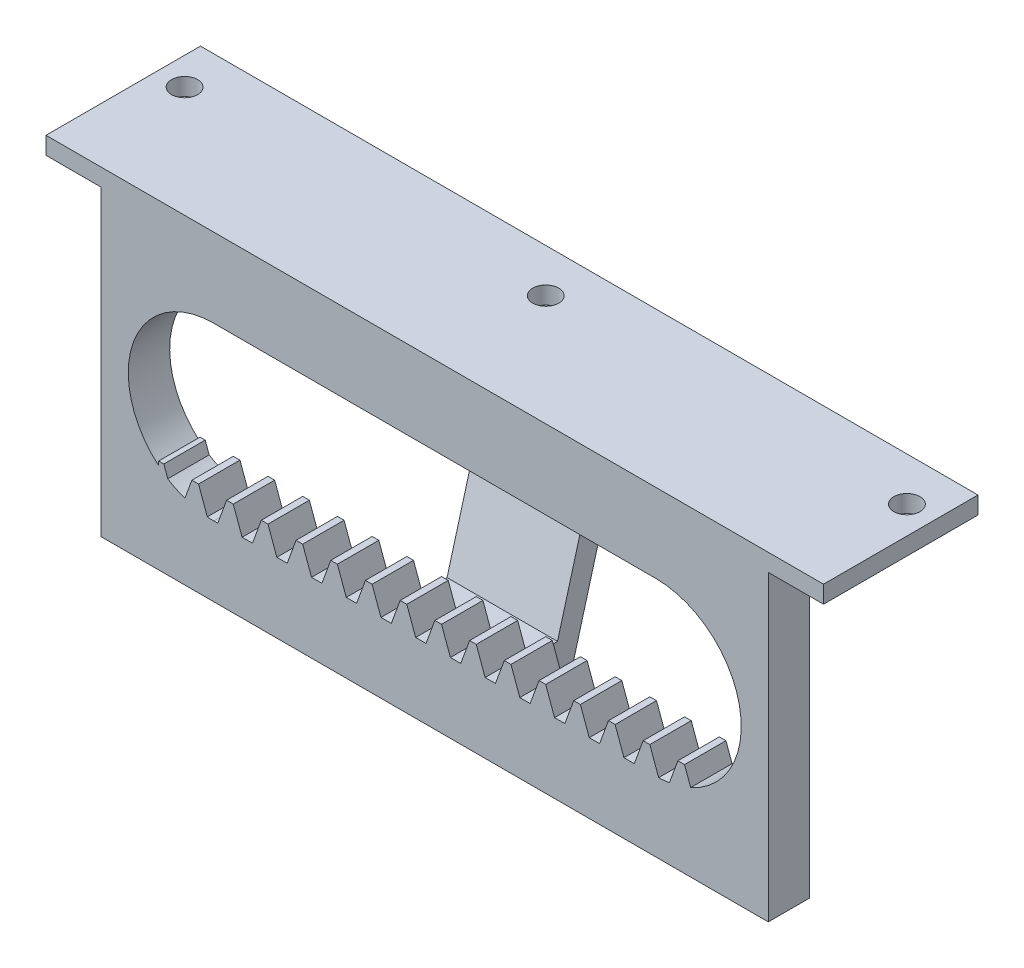
SolidWorks part; units mm, degrees
material "Nylon 101"
ref_plane "Front Plane" through (0, 0, 0) normal (0, 0, 1) x (1, 0, 0)
ref_plane "Top Plane" through (0, 0, 0) normal (0, 1, 0) x (1, 0, 0)
ref_plane "Right Plane" through (0, 0, 0) normal (1, 0, 0) x (0, 0, -1)
sketch "Sketch1" plane through (0, 0, 0) normal (0, 1, 0) x (1, 0, 0)
  line L0 (0, 0) -> (0, 4.7625)
  line L1 (0, 4.7625) -> (63.5, 4.7625)
  line L2 (63.5, 4.7625) -> (63.5, 0)
  line L3 (63.5, 0) -> (0, 0)
  dimension "D1" = 4.7625
  dimension "D2" = 63.5
extrude "Boss-Extrude1" add sketch "Sketch1" along normal blind 4.5
sketch "Sketch2" plane through (0, 0, 0) normal (0, 0, 1) x (1, 0, 0)
  line L0 (0, 3.2275) -> (63.5, 3.2275) construction
  line L1 (0, 4.5) -> (0, 0) construction
  line L2 (63.5, 4.5) -> (63.5, 0) construction
  line L3 (0, 1.7035) -> (63.5, 1.7035) construction
  line L4 (0, 4.5) -> (63.5, 4.5) construction
  line L5 (0, 4.5) -> (0.5952, 4.5) construction
  line L6 (0.5952, 4.5) -> (1.613, 1.7035)
  line L7 (1.613, 1.7035) -> (2.2082, 1.7035)
  line L8 (2.8034, 1.7035) -> (3.8212, 4.5)
  line L9 (3.8212, 4.5) -> (4.4164, 4.5) construction
  line L10 (2.2082, 1.7035) -> (2.8034, 1.7035)
  line L11 (0.5952, 4.5) -> (3.8212, 4.5)
  line L12 (4.5868, 4.5) -> (5.6047, 1.7035)
  line L13 (5.6047, 1.7035) -> (6.1999, 1.7035)
  line L14 (6.795, 1.7035) -> (7.8129, 4.5)
  line L15 (6.1999, 1.7035) -> (6.795, 1.7035)
  line L16 (4.5868, 4.5) -> (7.8129, 4.5)
  line L17 (3.9917, 4.5) -> (4.5868, 4.5) construction
  line L18 (7.8129, 4.5) -> (8.4081, 4.5) construction
  line L19 (8.5785, 4.5) -> (9.5964, 1.7035)
  line L20 (9.5964, 1.7035) -> (10.1915, 1.7035)
  line L21 (10.7867, 1.7035) -> (11.8046, 4.5)
  line L22 (10.1915, 1.7035) -> (10.7867, 1.7035)
  line L23 (8.5785, 4.5) -> (11.8046, 4.5)
  line L24 (7.9834, 4.5) -> (8.5785, 4.5) construction
  line L25 (11.8046, 4.5) -> (12.3997, 4.5) construction
  line L26 (12.5702, 4.5) -> (13.5881, 1.7035)
  line L27 (13.5881, 1.7035) -> (14.1832, 1.7035)
  line L28 (14.7784, 1.7035) -> (15.7962, 4.5)
  line L29 (14.1832, 1.7035) -> (14.7784, 1.7035)
  line L30 (12.5702, 4.5) -> (15.7962, 4.5)
  line L31 (11.975, 4.5) -> (12.5702, 4.5) construction
  line L32 (15.7962, 4.5) -> (16.3914, 4.5) construction
  line L33 (16.5619, 4.5) -> (17.5797, 1.7035)
  line L34 (17.5797, 1.7035) -> (18.1749, 1.7035)
  line L35 (18.7701, 1.7035) -> (19.7879, 4.5)
  line L36 (18.1749, 1.7035) -> (18.7701, 1.7035)
  line L37 (16.5619, 4.5) -> (19.7879, 4.5)
  line L38 (15.9667, 4.5) -> (16.5619, 4.5) construction
  line L39 (19.7879, 4.5) -> (20.3831, 4.5) construction
  line L40 (20.5535, 4.5) -> (21.5714, 1.7035)
  line L41 (21.5714, 1.7035) -> (22.1666, 1.7035)
  line L42 (22.7617, 1.7035) -> (23.7796, 4.5)
  line L43 (22.1666, 1.7035) -> (22.7617, 1.7035)
  line L44 (20.5535, 4.5) -> (23.7796, 4.5)
  line L45 (19.9584, 4.5) -> (20.5535, 4.5) construction
  line L46 (23.7796, 4.5) -> (24.3748, 4.5) construction
  line L47 (24.5452, 4.5) -> (25.5631, 1.7035)
  line L48 (25.5631, 1.7035) -> (26.1582, 1.7035)
  line L49 (26.7534, 1.7035) -> (27.7713, 4.5)
  line L50 (26.1582, 1.7035) -> (26.7534, 1.7035)
  line L51 (24.5452, 4.5) -> (27.7713, 4.5)
  line L52 (23.9501, 4.5) -> (24.5452, 4.5) construction
  line L53 (27.7713, 4.5) -> (28.3664, 4.5) construction
  line L54 (28.5369, 4.5) -> (29.5548, 1.7035)
  line L55 (29.5548, 1.7035) -> (30.1499, 1.7035)
  line L56 (30.7451, 1.7035) -> (31.763, 4.5)
  line L57 (30.1499, 1.7035) -> (30.7451, 1.7035)
  line L58 (28.5369, 4.5) -> (31.763, 4.5)
  line L59 (27.9417, 4.5) -> (28.5369, 4.5) construction
  line L60 (31.763, 4.5) -> (32.3581, 4.5) construction
  line L61 (32.5286, 4.5) -> (33.5464, 1.7035)
  line L62 (33.5464, 1.7035) -> (34.1416, 1.7035)
  line L63 (34.7368, 1.7035) -> (35.7546, 4.5)
  line L64 (34.1416, 1.7035) -> (34.7368, 1.7035)
  line L65 (32.5286, 4.5) -> (35.7546, 4.5)
  line L66 (31.9334, 4.5) -> (32.5286, 4.5) construction
  line L67 (35.7546, 4.5) -> (36.3498, 4.5) construction
  line L68 (36.5203, 4.5) -> (37.5381, 1.7035)
  line L69 (37.5381, 1.7035) -> (38.1333, 1.7035)
  line L70 (38.7284, 1.7035) -> (39.7463, 4.5)
  line L71 (38.1333, 1.7035) -> (38.7284, 1.7035)
  line L72 (36.5203, 4.5) -> (39.7463, 4.5)
  line L73 (35.9251, 4.5) -> (36.5203, 4.5) construction
  line L74 (39.7463, 4.5) -> (40.3415, 4.5) construction
  line L75 (40.5119, 4.5) -> (41.5298, 1.7035)
  line L76 (41.5298, 1.7035) -> (42.125, 1.7035)
  line L77 (42.7201, 1.7035) -> (43.738, 4.5)
  line L78 (42.125, 1.7035) -> (42.7201, 1.7035)
  line L79 (40.5119, 4.5) -> (43.738, 4.5)
  line L80 (39.9168, 4.5) -> (40.5119, 4.5) construction
  line L81 (43.738, 4.5) -> (44.3331, 4.5) construction
  line L82 (44.5036, 4.5) -> (45.5215, 1.7035)
  line L83 (45.5215, 1.7035) -> (46.1166, 1.7035)
  line L84 (46.7118, 1.7035) -> (47.7297, 4.5)
  line L85 (46.1166, 1.7035) -> (46.7118, 1.7035)
  line L86 (44.5036, 4.5) -> (47.7297, 4.5)
  line L87 (43.9084, 4.5) -> (44.5036, 4.5) construction
  line L88 (47.7297, 4.5) -> (48.3248, 4.5) construction
  line L89 (48.4953, 4.5) -> (49.5131, 1.7035)
  line L90 (49.5131, 1.7035) -> (50.1083, 1.7035)
  line L91 (50.7035, 1.7035) -> (51.7213, 4.5)
  line L92 (50.1083, 1.7035) -> (50.7035, 1.7035)
  line L93 (48.4953, 4.5) -> (51.7213, 4.5)
  line L94 (47.9001, 4.5) -> (48.4953, 4.5) construction
  line L95 (51.7213, 4.5) -> (52.3165, 4.5) construction
  line L96 (52.487, 4.5) -> (53.5048, 1.7035)
  line L97 (53.5048, 1.7035) -> (54.1, 1.7035)
  line L98 (54.6952, 1.7035) -> (55.713, 4.5)
  line L99 (54.1, 1.7035) -> (54.6952, 1.7035)
  line L100 (52.487, 4.5) -> (55.713, 4.5)
  line L101 (51.8918, 4.5) -> (52.487, 4.5) construction
  line L102 (55.713, 4.5) -> (56.3082, 4.5) construction
  line L103 (56.4786, 4.5) -> (57.4965, 1.7035)
  line L104 (57.4965, 1.7035) -> (58.0917, 1.7035)
  line L105 (58.6868, 1.7035) -> (59.7047, 4.5)
  line L106 (58.0917, 1.7035) -> (58.6868, 1.7035)
  line L107 (56.4786, 4.5) -> (59.7047, 4.5)
  line L108 (55.8835, 4.5) -> (56.4786, 4.5) construction
  line L109 (59.7047, 4.5) -> (60.2999, 4.5) construction
  line L110 (60.4703, 4.5) -> (61.4882, 1.7035)
  line L111 (61.4882, 1.7035) -> (62.0833, 1.7035)
  line L112 (62.6785, 1.7035) -> (63.6964, 4.5)
  line L113 (62.0833, 1.7035) -> (62.6785, 1.7035)
  line L114 (60.4703, 4.5) -> (63.6964, 4.5)
  line L115 (59.8751, 4.5) -> (60.4703, 4.5) construction
  line L116 (63.6964, 4.5) -> (64.2915, 4.5) construction
  line L117 (64.462, 4.5) -> (65.4798, 1.7035)
  line L118 (65.4798, 1.7035) -> (66.075, 1.7035)
  line L119 (66.6702, 1.7035) -> (67.688, 4.5)
  line L120 (66.075, 1.7035) -> (66.6702, 1.7035)
  line L121 (64.462, 4.5) -> (67.688, 4.5)
  line L122 (63.8668, 4.5) -> (64.462, 4.5) construction
  line L123 (67.688, 4.5) -> (68.2832, 4.5) construction
  line L124 (68.4537, 4.5) -> (69.4715, 1.7035)
  line L125 (69.4715, 1.7035) -> (70.0667, 1.7035)
  line L126 (70.6619, 1.7035) -> (71.6797, 4.5)
  line L127 (70.0667, 1.7035) -> (70.6619, 1.7035)
  line L128 (68.4537, 4.5) -> (71.6797, 4.5)
  line L129 (67.8585, 4.5) -> (68.4537, 4.5) construction
  line L130 (71.6797, 4.5) -> (72.2749, 4.5) construction
  line L131 (72.4453, 4.5) -> (73.4632, 1.7035)
  line L132 (73.4632, 1.7035) -> (74.0584, 1.7035)
  line L133 (74.6535, 1.7035) -> (75.6714, 4.5)
  line L134 (74.0584, 1.7035) -> (74.6535, 1.7035)
  line L135 (72.4453, 4.5) -> (75.6714, 4.5)
  line L136 (71.8502, 4.5) -> (72.4453, 4.5) construction
  line L137 (75.6714, 4.5) -> (76.2666, 4.5) construction
  line L138 (76.437, 4.5) -> (77.4549, 1.7035)
  line L139 (77.4549, 1.7035) -> (78.05, 1.7035)
  line L140 (78.6452, 1.7035) -> (79.6631, 4.5)
  line L141 (78.05, 1.7035) -> (78.6452, 1.7035)
  line L142 (76.437, 4.5) -> (79.6631, 4.5)
  line L143 (75.8418, 4.5) -> (76.437, 4.5) construction
  line L144 (79.6631, 4.5) -> (80.2582, 4.5) construction
  line L145 (80.4287, 4.5) -> (81.4465, 1.7035)
  line L146 (81.4465, 1.7035) -> (82.0417, 1.7035)
  line L147 (82.6369, 1.7035) -> (83.6547, 4.5)
  line L148 (82.0417, 1.7035) -> (82.6369, 1.7035)
  line L149 (80.4287, 4.5) -> (83.6547, 4.5)
  line L150 (79.8335, 4.5) -> (80.4287, 4.5) construction
  line L151 (83.6547, 4.5) -> (84.2499, 4.5) construction
  line L152 (84.4204, 4.5) -> (85.4382, 1.7035)
  line L153 (85.4382, 1.7035) -> (86.0334, 1.7035)
  line L154 (86.6286, 1.7035) -> (87.6464, 4.5)
  line L155 (86.0334, 1.7035) -> (86.6286, 1.7035)
  line L156 (84.4204, 4.5) -> (87.6464, 4.5)
  line L157 (83.8252, 4.5) -> (84.4204, 4.5) construction
  line L158 (87.6464, 4.5) -> (88.2416, 4.5) construction
  line L159 (88.412, 4.5) -> (89.4299, 1.7035)
  line L160 (89.4299, 1.7035) -> (90.0251, 1.7035)
  line L161 (90.6202, 1.7035) -> (91.6381, 4.5)
  line L162 (90.0251, 1.7035) -> (90.6202, 1.7035)
  line L163 (88.412, 4.5) -> (91.6381, 4.5)
  line L164 (87.8169, 4.5) -> (88.412, 4.5) construction
  line L165 (91.6381, 4.5) -> (92.2333, 4.5) construction
  line L166 (92.4037, 4.5) -> (93.4216, 1.7035)
  line L167 (93.4216, 1.7035) -> (94.0167, 1.7035)
  line L168 (94.6119, 1.7035) -> (95.6298, 4.5)
  line L169 (94.0167, 1.7035) -> (94.6119, 1.7035)
  line L170 (92.4037, 4.5) -> (95.6298, 4.5)
  line L171 (91.8086, 4.5) -> (92.4037, 4.5) construction
  line L172 (95.6298, 4.5) -> (96.2249, 4.5) construction
  line L173 (96.3954, 4.5) -> (97.4133, 1.7035)
  line L174 (97.4133, 1.7035) -> (98.0084, 1.7035)
  line L175 (98.6036, 1.7035) -> (99.6214, 4.5)
  line L176 (98.0084, 1.7035) -> (98.6036, 1.7035)
  line L177 (96.3954, 4.5) -> (99.6214, 4.5)
  line L178 (95.8002, 4.5) -> (96.3954, 4.5) construction
  line L179 (99.6214, 4.5) -> (100.2166, 4.5) construction
  line L180 (100.3871, 4.5) -> (101.4049, 1.7035)
  line L181 (101.4049, 1.7035) -> (102.0001, 1.7035)
  line L182 (102.5953, 1.7035) -> (103.6131, 4.5)
  line L183 (102.0001, 1.7035) -> (102.5953, 1.7035)
  line L184 (100.3871, 4.5) -> (103.6131, 4.5)
  line L185 (99.7919, 4.5) -> (100.3871, 4.5) construction
  line L186 (103.6131, 4.5) -> (104.2083, 4.5) construction
  line L187 (104.3787, 4.5) -> (105.3966, 1.7035)
  line L188 (105.3966, 1.7035) -> (105.9918, 1.7035)
  line L189 (106.5869, 1.7035) -> (107.6048, 4.5)
  line L190 (105.9918, 1.7035) -> (106.5869, 1.7035)
  line L191 (104.3787, 4.5) -> (107.6048, 4.5)
  line L192 (103.7836, 4.5) -> (104.3787, 4.5) construction
  line L193 (107.6048, 4.5) -> (108.2, 4.5) construction
  line L194 (108.3704, 4.5) -> (109.3883, 1.7035)
  line L195 (109.3883, 1.7035) -> (109.9835, 1.7035)
  line L196 (110.5786, 1.7035) -> (111.5965, 4.5)
  line L197 (109.9835, 1.7035) -> (110.5786, 1.7035)
  line L198 (108.3704, 4.5) -> (111.5965, 4.5)
  line L199 (107.7753, 4.5) -> (108.3704, 4.5) construction
  line L200 (111.5965, 4.5) -> (112.1916, 4.5) construction
  line L201 (112.3621, 4.5) -> (113.38, 1.7035)
  line L202 (113.38, 1.7035) -> (113.9751, 1.7035)
  line L203 (114.5703, 1.7035) -> (115.5882, 4.5)
  line L204 (113.9751, 1.7035) -> (114.5703, 1.7035)
  line L205 (112.3621, 4.5) -> (115.5882, 4.5)
  line L206 (111.7669, 4.5) -> (112.3621, 4.5) construction
  line L207 (115.5882, 4.5) -> (116.1833, 4.5) construction
  line L208 (116.3538, 4.5) -> (117.3716, 1.7035)
  line L209 (117.3716, 1.7035) -> (117.9668, 1.7035)
  line L210 (118.562, 1.7035) -> (119.5798, 4.5)
  line L211 (117.9668, 1.7035) -> (118.562, 1.7035)
  line L212 (116.3538, 4.5) -> (119.5798, 4.5)
  line L213 (115.7586, 4.5) -> (116.3538, 4.5) construction
  line L214 (119.5798, 4.5) -> (120.175, 4.5) construction
  line L215 (120.3455, 4.5) -> (121.3633, 1.7035)
  line L216 (121.3633, 1.7035) -> (121.9585, 1.7035)
  line L217 (122.5536, 1.7035) -> (123.5715, 4.5)
  line L218 (121.9585, 1.7035) -> (122.5536, 1.7035)
  line L219 (120.3455, 4.5) -> (123.5715, 4.5)
  line L220 (119.7503, 4.5) -> (120.3455, 4.5) construction
  line L221 (123.5715, 4.5) -> (124.1667, 4.5) construction
  line L222 (124.3371, 4.5) -> (125.355, 1.7035)
  line L223 (125.355, 1.7035) -> (125.9502, 1.7035)
  line L224 (126.5453, 1.7035) -> (127.5632, 4.5)
  line L225 (125.9502, 1.7035) -> (126.5453, 1.7035)
  line L226 (124.3371, 4.5) -> (127.5632, 4.5)
  line L227 (123.742, 4.5) -> (124.3371, 4.5) construction
  line L228 (127.5632, 4.5) -> (128.1583, 4.5) construction
  line L229 (128.3288, 4.5) -> (129.3467, 1.7035)
  line L230 (129.3467, 1.7035) -> (129.9418, 1.7035)
  line L231 (130.537, 1.7035) -> (131.5549, 4.5)
  line L232 (129.9418, 1.7035) -> (130.537, 1.7035)
  line L233 (128.3288, 4.5) -> (131.5549, 4.5)
  line L234 (127.7336, 4.5) -> (128.3288, 4.5) construction
  line L235 (131.5549, 4.5) -> (132.15, 4.5) construction
  line L236 (132.3205, 4.5) -> (133.3383, 1.7035)
  line L237 (133.3383, 1.7035) -> (133.9335, 1.7035)
  line L238 (134.5287, 1.7035) -> (135.5465, 4.5)
  line L239 (133.9335, 1.7035) -> (134.5287, 1.7035)
  line L240 (132.3205, 4.5) -> (135.5465, 4.5)
  line L241 (131.7253, 4.5) -> (132.3205, 4.5) construction
  line L242 (135.5465, 4.5) -> (136.1417, 4.5) construction
  line L243 (136.3122, 4.5) -> (137.33, 1.7035)
  line L244 (137.33, 1.7035) -> (137.9252, 1.7035)
  line L245 (138.5204, 1.7035) -> (139.5382, 4.5)
  line L246 (137.9252, 1.7035) -> (138.5204, 1.7035)
  line L247 (136.3122, 4.5) -> (139.5382, 4.5)
  line L248 (135.717, 4.5) -> (136.3122, 4.5) construction
  line L249 (139.5382, 4.5) -> (140.1334, 4.5) construction
  line L250 (140.3038, 4.5) -> (141.3217, 1.7035)
  line L251 (141.3217, 1.7035) -> (141.9169, 1.7035)
  line L252 (142.512, 1.7035) -> (143.5299, 4.5)
  line L253 (141.9169, 1.7035) -> (142.512, 1.7035)
  line L254 (140.3038, 4.5) -> (143.5299, 4.5)
  line L255 (139.7087, 4.5) -> (140.3038, 4.5) construction
  line L256 (143.5299, 4.5) -> (144.1251, 4.5) construction
  line L257 (144.2955, 4.5) -> (145.3134, 1.7035)
  line L258 (145.3134, 1.7035) -> (145.9085, 1.7035)
  line L259 (146.5037, 1.7035) -> (147.5216, 4.5)
  line L260 (145.9085, 1.7035) -> (146.5037, 1.7035)
  line L261 (144.2955, 4.5) -> (147.5216, 4.5)
  line L262 (143.7003, 4.5) -> (144.2955, 4.5) construction
  line L263 (147.5216, 4.5) -> (148.1167, 4.5) construction
  line L264 (148.2872, 4.5) -> (149.305, 1.7035)
  line L265 (149.305, 1.7035) -> (149.9002, 1.7035)
  line L266 (150.4954, 1.7035) -> (151.5132, 4.5)
  line L267 (149.9002, 1.7035) -> (150.4954, 1.7035)
  line L268 (148.2872, 4.5) -> (151.5132, 4.5)
  line L269 (147.692, 4.5) -> (148.2872, 4.5) construction
  line L270 (151.5132, 4.5) -> (152.1084, 4.5) construction
  line L271 (152.2789, 4.5) -> (153.2967, 1.7035)
  line L272 (153.2967, 1.7035) -> (153.8919, 1.7035)
  line L273 (154.4871, 1.7035) -> (155.5049, 4.5)
  line L274 (153.8919, 1.7035) -> (154.4871, 1.7035)
  line L275 (152.2789, 4.5) -> (155.5049, 4.5)
  line L276 (151.6837, 4.5) -> (152.2789, 4.5) construction
  line L277 (155.5049, 4.5) -> (156.1001, 4.5) construction
  line L278 (156.2705, 4.5) -> (157.2884, 1.7035)
  line L279 (157.2884, 1.7035) -> (157.8836, 1.7035)
  line L280 (158.4787, 1.7035) -> (159.4966, 4.5)
  line L281 (157.8836, 1.7035) -> (158.4787, 1.7035)
  line L282 (156.2705, 4.5) -> (159.4966, 4.5)
  line L283 (155.6754, 4.5) -> (156.2705, 4.5) construction
  line L284 (159.4966, 4.5) -> (160.0918, 4.5) construction
  line L285 (160.2622, 4.5) -> (161.2801, 1.7035)
  line L286 (161.2801, 1.7035) -> (161.8752, 1.7035)
  line L287 (162.4704, 1.7035) -> (163.4883, 4.5)
  line L288 (161.8752, 1.7035) -> (162.4704, 1.7035)
  line L289 (160.2622, 4.5) -> (163.4883, 4.5)
  line L290 (159.667, 4.5) -> (160.2622, 4.5) construction
  line L291 (163.4883, 4.5) -> (164.0834, 4.5) construction
  line L292 (164.2539, 4.5) -> (165.2718, 1.7035)
  line L293 (165.2718, 1.7035) -> (165.8669, 1.7035)
  line L294 (166.4621, 1.7035) -> (167.4799, 4.5)
  line L295 (165.8669, 1.7035) -> (166.4621, 1.7035)
  line L296 (164.2539, 4.5) -> (167.4799, 4.5)
  line L297 (163.6587, 4.5) -> (164.2539, 4.5) construction
  line L298 (167.4799, 4.5) -> (168.0751, 4.5) construction
  line L299 (168.2456, 4.5) -> (169.2634, 1.7035)
  line L300 (169.2634, 1.7035) -> (169.8586, 1.7035)
  line L301 (170.4538, 1.7035) -> (171.4716, 4.5)
  line L302 (169.8586, 1.7035) -> (170.4538, 1.7035)
  line L303 (168.2456, 4.5) -> (171.4716, 4.5)
  line L304 (167.6504, 4.5) -> (168.2456, 4.5) construction
  line L305 (171.4716, 4.5) -> (172.0668, 4.5) construction
  line L306 (172.2372, 4.5) -> (173.2551, 1.7035)
  line L307 (173.2551, 1.7035) -> (173.8503, 1.7035)
  line L308 (174.4454, 1.7035) -> (175.4633, 4.5)
  line L309 (173.8503, 1.7035) -> (174.4454, 1.7035)
  line L310 (172.2372, 4.5) -> (175.4633, 4.5)
  line L311 (171.6421, 4.5) -> (172.2372, 4.5) construction
  line L312 (175.4633, 4.5) -> (176.0585, 4.5) construction
  line L313 (176.2289, 4.5) -> (177.2468, 1.7035)
  line L314 (177.2468, 1.7035) -> (177.8419, 1.7035)
  line L315 (178.4371, 1.7035) -> (179.455, 4.5)
  line L316 (177.8419, 1.7035) -> (178.4371, 1.7035)
  line L317 (176.2289, 4.5) -> (179.455, 4.5)
  line L318 (175.6338, 4.5) -> (176.2289, 4.5) construction
  line L319 (179.455, 4.5) -> (180.0501, 4.5) construction
  line L320 (180.2206, 4.5) -> (181.2385, 1.7035)
  line L321 (181.2385, 1.7035) -> (181.8336, 1.7035)
  line L322 (182.4288, 1.7035) -> (183.4466, 4.5)
  line L323 (181.8336, 1.7035) -> (182.4288, 1.7035)
  line L324 (180.2206, 4.5) -> (183.4466, 4.5)
  line L325 (179.6254, 4.5) -> (180.2206, 4.5) construction
  line L326 (183.4466, 4.5) -> (184.0418, 4.5) construction
  line L327 (184.2123, 4.5) -> (185.2301, 1.7035)
  line L328 (185.2301, 1.7035) -> (185.8253, 1.7035)
  line L329 (186.4205, 1.7035) -> (187.4383, 4.5)
  line L330 (185.8253, 1.7035) -> (186.4205, 1.7035)
  line L331 (184.2123, 4.5) -> (187.4383, 4.5)
  line L332 (183.6171, 4.5) -> (184.2123, 4.5) construction
  line L333 (187.4383, 4.5) -> (188.0335, 4.5) construction
  line L334 (188.204, 4.5) -> (189.2218, 1.7035)
  line L335 (189.2218, 1.7035) -> (189.817, 1.7035)
  line L336 (190.4121, 1.7035) -> (191.43, 4.5)
  line L337 (189.817, 1.7035) -> (190.4121, 1.7035)
  line L338 (188.204, 4.5) -> (191.43, 4.5)
  line L339 (187.6088, 4.5) -> (188.204, 4.5) construction
  line L340 (191.43, 4.5) -> (192.0252, 4.5) construction
  line L341 (192.1956, 4.5) -> (193.2135, 1.7035)
  line L342 (193.2135, 1.7035) -> (193.8087, 1.7035)
  line L343 (194.4038, 1.7035) -> (195.4217, 4.5)
  line L344 (193.8087, 1.7035) -> (194.4038, 1.7035)
  line L345 (192.1956, 4.5) -> (195.4217, 4.5)
  line L346 (191.6005, 4.5) -> (192.1956, 4.5) construction
  line L347 (195.4217, 4.5) -> (196.0168, 4.5) construction
  line L348 (196.1873, 4.5) -> (197.2052, 1.7035)
  line L349 (197.2052, 1.7035) -> (197.8003, 1.7035)
  line L350 (198.3955, 1.7035) -> (199.4134, 4.5)
  line L351 (197.8003, 1.7035) -> (198.3955, 1.7035)
  line L352 (196.1873, 4.5) -> (199.4134, 4.5)
  line L353 (195.5921, 4.5) -> (196.1873, 4.5) construction
  line L354 (199.4134, 4.5) -> (200.0085, 4.5) construction
  line L355 (200.179, 4.5) -> (201.1968, 1.7035)
  line L356 (201.1968, 1.7035) -> (201.792, 1.7035)
  line L357 (202.3872, 1.7035) -> (203.405, 4.5)
  line L358 (201.792, 1.7035) -> (202.3872, 1.7035)
  line L359 (200.179, 4.5) -> (203.405, 4.5)
  line L360 (199.5838, 4.5) -> (200.179, 4.5) construction
  line L361 (203.405, 4.5) -> (204.0002, 4.5) construction
  line L362 (204.1707, 4.5) -> (205.1885, 1.7035)
  line L363 (205.1885, 1.7035) -> (205.7837, 1.7035)
  line L364 (206.3788, 1.7035) -> (207.3967, 4.5)
  line L365 (205.7837, 1.7035) -> (206.3788, 1.7035)
  line L366 (204.1707, 4.5) -> (207.3967, 4.5)
  line L367 (203.5755, 4.5) -> (204.1707, 4.5) construction
  line L368 (207.3967, 4.5) -> (207.9919, 4.5) construction
  line L369 (208.1623, 4.5) -> (209.1802, 1.7035)
  line L370 (209.1802, 1.7035) -> (209.7754, 1.7035)
  line L371 (210.3705, 1.7035) -> (211.3884, 4.5)
  line L372 (209.7754, 1.7035) -> (210.3705, 1.7035)
  line L373 (208.1623, 4.5) -> (211.3884, 4.5)
  line L374 (207.5672, 4.5) -> (208.1623, 4.5) construction
  line L375 (211.3884, 4.5) -> (211.9835, 4.5) construction
  line L376 (212.154, 4.5) -> (213.1719, 1.7035)
  line L377 (213.1719, 1.7035) -> (213.767, 1.7035)
  line L378 (214.3622, 1.7035) -> (215.3801, 4.5)
  line L379 (213.767, 1.7035) -> (214.3622, 1.7035)
  line L380 (212.154, 4.5) -> (215.3801, 4.5)
  line L381 (211.5588, 4.5) -> (212.154, 4.5) construction
  line L382 (215.3801, 4.5) -> (215.9752, 4.5) construction
  line L383 (216.1457, 4.5) -> (217.1635, 1.7035)
  line L384 (217.1635, 1.7035) -> (217.7587, 1.7035)
  line L385 (218.3539, 1.7035) -> (219.3717, 4.5)
  line L386 (217.7587, 1.7035) -> (218.3539, 1.7035)
  line L387 (216.1457, 4.5) -> (219.3717, 4.5)
  line L388 (215.5505, 4.5) -> (216.1457, 4.5) construction
  line L389 (219.3717, 4.5) -> (219.9669, 4.5) construction
  line L390 (220.1374, 4.5) -> (221.1552, 1.7035)
  line L391 (221.1552, 1.7035) -> (221.7504, 1.7035)
  line L392 (222.3456, 1.7035) -> (223.3634, 4.5)
  line L393 (221.7504, 1.7035) -> (222.3456, 1.7035)
  line L394 (220.1374, 4.5) -> (223.3634, 4.5)
  line L395 (219.5422, 4.5) -> (220.1374, 4.5) construction
  line L396 (223.3634, 4.5) -> (223.9586, 4.5) construction
  line L397 (224.129, 4.5) -> (225.1469, 1.7035)
  line L398 (225.1469, 1.7035) -> (225.7421, 1.7035)
  line L399 (226.3372, 1.7035) -> (227.3551, 4.5)
  line L400 (225.7421, 1.7035) -> (226.3372, 1.7035)
  line L401 (224.129, 4.5) -> (227.3551, 4.5)
  line L402 (223.5339, 4.5) -> (224.129, 4.5) construction
  line L403 (227.3551, 4.5) -> (227.9503, 4.5) construction
  line L404 (228.1207, 4.5) -> (229.1386, 1.7035)
  line L405 (229.1386, 1.7035) -> (229.7337, 1.7035)
  line L406 (230.3289, 1.7035) -> (231.3468, 4.5)
  line L407 (229.7337, 1.7035) -> (230.3289, 1.7035)
  line L408 (228.1207, 4.5) -> (231.3468, 4.5)
  line L409 (227.5255, 4.5) -> (228.1207, 4.5) construction
  line L410 (231.3468, 4.5) -> (231.9419, 4.5) construction
  line L411 (232.1124, 4.5) -> (233.1302, 1.7035)
  line L412 (233.1302, 1.7035) -> (233.7254, 1.7035)
  line L413 (234.3206, 1.7035) -> (235.3384, 4.5)
  line L414 (233.7254, 1.7035) -> (234.3206, 1.7035)
  line L415 (232.1124, 4.5) -> (235.3384, 4.5)
  line L416 (231.5172, 4.5) -> (232.1124, 4.5) construction
  line L417 (235.3384, 4.5) -> (235.9336, 4.5) construction
  line L418 (236.1041, 4.5) -> (237.1219, 1.7035)
  line L419 (237.1219, 1.7035) -> (237.7171, 1.7035)
  line L420 (238.3123, 1.7035) -> (239.3301, 4.5)
  line L421 (237.7171, 1.7035) -> (238.3123, 1.7035)
  line L422 (236.1041, 4.5) -> (239.3301, 4.5)
  line L423 (235.5089, 4.5) -> (236.1041, 4.5) construction
  line L424 (239.3301, 4.5) -> (239.9253, 4.5) construction
  line L425 (240.0957, 4.5) -> (241.1136, 1.7035)
  line L426 (241.1136, 1.7035) -> (241.7088, 1.7035)
  line L427 (242.3039, 1.7035) -> (243.3218, 4.5)
  line L428 (241.7088, 1.7035) -> (242.3039, 1.7035)
  line L429 (240.0957, 4.5) -> (243.3218, 4.5)
  line L430 (239.5006, 4.5) -> (240.0957, 4.5) construction
  line L431 (243.3218, 4.5) -> (243.917, 4.5) construction
  line L432 (244.0874, 4.5) -> (245.1053, 1.7035)
  line L433 (245.1053, 1.7035) -> (245.7004, 1.7035)
  line L434 (246.2956, 1.7035) -> (247.3135, 4.5)
  line L435 (245.7004, 1.7035) -> (246.2956, 1.7035)
  line L436 (244.0874, 4.5) -> (247.3135, 4.5)
  line L437 (243.4923, 4.5) -> (244.0874, 4.5) construction
  line L438 (247.3135, 4.5) -> (247.9086, 4.5) construction
  line L439 (248.0791, 4.5) -> (249.097, 1.7035)
  line L440 (249.097, 1.7035) -> (249.6921, 1.7035)
  line L441 (250.2873, 1.7035) -> (251.3051, 4.5)
  line L442 (249.6921, 1.7035) -> (250.2873, 1.7035)
  line L443 (248.0791, 4.5) -> (251.3051, 4.5)
  line L444 (247.4839, 4.5) -> (248.0791, 4.5) construction
  line L445 (251.3051, 4.5) -> (251.9003, 4.5) construction
  line L446 (252.0708, 4.5) -> (253.0886, 1.7035)
  line L447 (253.0886, 1.7035) -> (253.6838, 1.7035)
  line L448 (254.279, 1.7035) -> (255.2968, 4.5)
  line L449 (253.6838, 1.7035) -> (254.279, 1.7035)
  line L450 (252.0708, 4.5) -> (255.2968, 4.5)
  line L451 (251.4756, 4.5) -> (252.0708, 4.5) construction
  line L452 (255.2968, 4.5) -> (255.892, 4.5) construction
  line L453 (256.0624, 4.5) -> (257.0803, 1.7035)
  line L454 (257.0803, 1.7035) -> (257.6755, 1.7035)
  line L455 (258.2706, 1.7035) -> (259.2885, 4.5)
  line L456 (257.6755, 1.7035) -> (258.2706, 1.7035)
  line L457 (256.0624, 4.5) -> (259.2885, 4.5)
  line L458 (255.4673, 4.5) -> (256.0624, 4.5) construction
  line L459 (259.2885, 4.5) -> (259.8837, 4.5) construction
  line L460 (260.0541, 4.5) -> (261.072, 1.7035)
  line L461 (261.072, 1.7035) -> (261.6671, 1.7035)
  line L462 (262.2623, 1.7035) -> (263.2802, 4.5)
  line L463 (261.6671, 1.7035) -> (262.2623, 1.7035)
  line L464 (260.0541, 4.5) -> (263.2802, 4.5)
  line L465 (259.459, 4.5) -> (260.0541, 4.5) construction
  line L466 (263.2802, 4.5) -> (263.8753, 4.5) construction
  line L467 (264.0458, 4.5) -> (265.0637, 1.7035)
  line L468 (265.0637, 1.7035) -> (265.6588, 1.7035)
  line L469 (266.254, 1.7035) -> (267.2718, 4.5)
  line L470 (265.6588, 1.7035) -> (266.254, 1.7035)
  line L471 (264.0458, 4.5) -> (267.2718, 4.5)
  line L472 (263.4506, 4.5) -> (264.0458, 4.5) construction
  line L473 (267.2718, 4.5) -> (267.867, 4.5) construction
  line L474 (268.0375, 4.5) -> (269.0553, 1.7035)
  line L475 (269.0553, 1.7035) -> (269.6505, 1.7035)
  line L476 (270.2457, 1.7035) -> (271.2635, 4.5)
  line L477 (269.6505, 1.7035) -> (270.2457, 1.7035)
  line L478 (268.0375, 4.5) -> (271.2635, 4.5)
  line L479 (267.4423, 4.5) -> (268.0375, 4.5) construction
  line L480 (271.2635, 4.5) -> (271.8587, 4.5) construction
  line L481 (272.0292, 4.5) -> (273.047, 1.7035)
  line L482 (273.047, 1.7035) -> (273.6422, 1.7035)
  line L483 (274.2373, 1.7035) -> (275.2552, 4.5)
  line L484 (273.6422, 1.7035) -> (274.2373, 1.7035)
  line L485 (272.0292, 4.5) -> (275.2552, 4.5)
  line L486 (271.434, 4.5) -> (272.0292, 4.5) construction
  line L487 (275.2552, 4.5) -> (275.8504, 4.5) construction
  line L488 (276.0208, 4.5) -> (277.0387, 1.7035)
  line L489 (277.0387, 1.7035) -> (277.6339, 1.7035)
  line L490 (278.229, 1.7035) -> (279.2469, 4.5)
  line L491 (277.6339, 1.7035) -> (278.229, 1.7035)
  line L492 (276.0208, 4.5) -> (279.2469, 4.5)
  line L493 (275.4257, 4.5) -> (276.0208, 4.5) construction
  line L494 (279.2469, 4.5) -> (279.842, 4.5) construction
  line L495 (280.0125, 4.5) -> (281.0304, 1.7035)
  line L496 (281.0304, 1.7035) -> (281.6255, 1.7035)
  line L497 (282.2207, 1.7035) -> (283.2386, 4.5)
  line L498 (281.6255, 1.7035) -> (282.2207, 1.7035)
  line L499 (280.0125, 4.5) -> (283.2386, 4.5)
  line L500 (279.4173, 4.5) -> (280.0125, 4.5) construction
  line L501 (283.2386, 4.5) -> (283.8337, 4.5) construction
  line L502 (284.0042, 4.5) -> (285.022, 1.7035)
  line L503 (285.022, 1.7035) -> (285.6172, 1.7035)
  line L504 (286.2124, 1.7035) -> (287.2302, 4.5)
  line L505 (285.6172, 1.7035) -> (286.2124, 1.7035)
  line L506 (284.0042, 4.5) -> (287.2302, 4.5)
  line L507 (283.409, 4.5) -> (284.0042, 4.5) construction
  line L508 (287.2302, 4.5) -> (287.8254, 4.5) construction
  line L509 (287.9959, 4.5) -> (289.0137, 1.7035)
  line L510 (289.0137, 1.7035) -> (289.6089, 1.7035)
  line L511 (290.204, 1.7035) -> (291.2219, 4.5)
  line L512 (289.6089, 1.7035) -> (290.204, 1.7035)
  line L513 (287.9959, 4.5) -> (291.2219, 4.5)
  line L514 (287.4007, 4.5) -> (287.9959, 4.5) construction
  line L515 (291.2219, 4.5) -> (291.8171, 4.5) construction
  line L516 (291.9875, 4.5) -> (293.0054, 1.7035)
  line L517 (293.0054, 1.7035) -> (293.6006, 1.7035)
  line L518 (294.1957, 1.7035) -> (295.2136, 4.5)
  line L519 (293.6006, 1.7035) -> (294.1957, 1.7035)
  line L520 (291.9875, 4.5) -> (295.2136, 4.5)
  line L521 (291.3924, 4.5) -> (291.9875, 4.5) construction
  line L522 (295.2136, 4.5) -> (295.8087, 4.5) construction
  line L523 (295.9792, 4.5) -> (296.9971, 1.7035)
  line L524 (296.9971, 1.7035) -> (297.5922, 1.7035)
  line L525 (298.1874, 1.7035) -> (299.2053, 4.5)
  line L526 (297.5922, 1.7035) -> (298.1874, 1.7035)
  line L527 (295.9792, 4.5) -> (299.2053, 4.5)
  line L528 (295.384, 4.5) -> (295.9792, 4.5) construction
  line L529 (299.2053, 4.5) -> (299.8004, 4.5) construction
  line L530 (299.9709, 4.5) -> (300.9887, 1.7035)
  line L531 (300.9887, 1.7035) -> (301.5839, 1.7035)
  line L532 (302.1791, 1.7035) -> (303.1969, 4.5)
  line L533 (301.5839, 1.7035) -> (302.1791, 1.7035)
  line L534 (299.9709, 4.5) -> (303.1969, 4.5)
  line L535 (299.3757, 4.5) -> (299.9709, 4.5) construction
  line L536 (303.1969, 4.5) -> (303.7921, 4.5) construction
  line L537 (303.9626, 4.5) -> (304.9804, 1.7035)
  line L538 (304.9804, 1.7035) -> (305.5756, 1.7035)
  line L539 (306.1708, 1.7035) -> (307.1886, 4.5)
  line L540 (305.5756, 1.7035) -> (306.1708, 1.7035)
  line L541 (303.9626, 4.5) -> (307.1886, 4.5)
  line L542 (303.3674, 4.5) -> (303.9626, 4.5) construction
  line L543 (307.1886, 4.5) -> (307.7838, 4.5) construction
  line L544 (307.9542, 4.5) -> (308.9721, 1.7035)
  line L545 (308.9721, 1.7035) -> (309.5673, 1.7035)
  line L546 (310.1624, 1.7035) -> (311.1803, 4.5)
  line L547 (309.5673, 1.7035) -> (310.1624, 1.7035)
  line L548 (307.9542, 4.5) -> (311.1803, 4.5)
  line L549 (307.3591, 4.5) -> (307.9542, 4.5) construction
  line L550 (311.1803, 4.5) -> (311.7755, 4.5) construction
  line L551 (311.9459, 4.5) -> (312.9638, 1.7035)
  line L552 (312.9638, 1.7035) -> (313.5589, 1.7035)
  line L553 (314.1541, 1.7035) -> (315.172, 4.5)
  line L554 (313.5589, 1.7035) -> (314.1541, 1.7035)
  line L555 (311.9459, 4.5) -> (315.172, 4.5)
  line L556 (311.3507, 4.5) -> (311.9459, 4.5) construction
  line L557 (315.172, 4.5) -> (315.7671, 4.5) construction
  line L558 (315.9376, 4.5) -> (316.9554, 1.7035)
  line L559 (316.9554, 1.7035) -> (317.5506, 1.7035)
  line L560 (318.1458, 1.7035) -> (319.1636, 4.5)
  line L561 (317.5506, 1.7035) -> (318.1458, 1.7035)
  line L562 (315.9376, 4.5) -> (319.1636, 4.5)
  line L563 (315.3424, 4.5) -> (315.9376, 4.5) construction
  line L564 (319.1636, 4.5) -> (319.7588, 4.5) construction
  line L565 (319.9293, 4.5) -> (320.9471, 1.7035)
  line L566 (320.9471, 1.7035) -> (321.5423, 1.7035)
  line L567 (322.1375, 1.7035) -> (323.1553, 4.5)
  line L568 (321.5423, 1.7035) -> (322.1375, 1.7035)
  line L569 (319.9293, 4.5) -> (323.1553, 4.5)
  line L570 (319.3341, 4.5) -> (319.9293, 4.5) construction
  line L571 (323.1553, 4.5) -> (323.7505, 4.5) construction
  line L572 (323.9209, 4.5) -> (324.9388, 1.7035)
  line L573 (324.9388, 1.7035) -> (325.534, 1.7035)
  line L574 (326.1291, 1.7035) -> (327.147, 4.5)
  line L575 (325.534, 1.7035) -> (326.1291, 1.7035)
  line L576 (323.9209, 4.5) -> (327.147, 4.5)
  line L577 (323.3258, 4.5) -> (323.9209, 4.5) construction
  line L578 (327.147, 4.5) -> (327.7422, 4.5) construction
  line L579 (327.9126, 4.5) -> (328.9305, 1.7035)
  line L580 (328.9305, 1.7035) -> (329.5256, 1.7035)
  line L581 (330.1208, 1.7035) -> (331.1387, 4.5)
  line L582 (329.5256, 1.7035) -> (330.1208, 1.7035)
  line L583 (327.9126, 4.5) -> (331.1387, 4.5)
  line L584 (327.3175, 4.5) -> (327.9126, 4.5) construction
  line L585 (331.1387, 4.5) -> (331.7338, 4.5) construction
  line L586 (331.9043, 4.5) -> (332.9222, 1.7035)
  line L587 (332.9222, 1.7035) -> (333.5173, 1.7035)
  line L588 (334.1125, 1.7035) -> (335.1303, 4.5)
  line L589 (333.5173, 1.7035) -> (334.1125, 1.7035)
  line L590 (331.9043, 4.5) -> (335.1303, 4.5)
  line L591 (331.3091, 4.5) -> (331.9043, 4.5) construction
  line L592 (335.1303, 4.5) -> (335.7255, 4.5) construction
  line L593 (335.896, 4.5) -> (336.9138, 1.7035)
  line L594 (336.9138, 1.7035) -> (337.509, 1.7035)
  line L595 (338.1042, 1.7035) -> (339.122, 4.5)
  line L596 (337.509, 1.7035) -> (338.1042, 1.7035)
  line L597 (335.896, 4.5) -> (339.122, 4.5)
  line L598 (335.3008, 4.5) -> (335.896, 4.5) construction
  line L599 (339.122, 4.5) -> (339.7172, 4.5) construction
  line L600 (339.8876, 4.5) -> (340.9055, 1.7035)
  line L601 (340.9055, 1.7035) -> (341.5007, 1.7035)
  line L602 (342.0958, 1.7035) -> (343.1137, 4.5)
  line L603 (341.5007, 1.7035) -> (342.0958, 1.7035)
  line L604 (339.8876, 4.5) -> (343.1137, 4.5)
  line L605 (339.2925, 4.5) -> (339.8876, 4.5) construction
  line L606 (343.1137, 4.5) -> (343.7089, 4.5) construction
  line L607 (343.8793, 4.5) -> (344.8972, 1.7035)
  line L608 (344.8972, 1.7035) -> (345.4923, 1.7035)
  line L609 (346.0875, 1.7035) -> (347.1054, 4.5)
  line L610 (345.4923, 1.7035) -> (346.0875, 1.7035)
  line L611 (343.8793, 4.5) -> (347.1054, 4.5)
  line L612 (343.2842, 4.5) -> (343.8793, 4.5) construction
  line L613 (347.1054, 4.5) -> (347.7005, 4.5) construction
  line L614 (347.871, 4.5) -> (348.8889, 1.7035)
  line L615 (348.8889, 1.7035) -> (349.484, 1.7035)
  line L616 (350.0792, 1.7035) -> (351.097, 4.5)
  line L617 (349.484, 1.7035) -> (350.0792, 1.7035)
  line L618 (347.871, 4.5) -> (351.097, 4.5)
  line L619 (347.2758, 4.5) -> (347.871, 4.5) construction
  line L620 (351.097, 4.5) -> (351.6922, 4.5) construction
  line L621 (351.8627, 4.5) -> (352.8805, 1.7035)
  line L622 (352.8805, 1.7035) -> (353.4757, 1.7035)
  line L623 (354.0709, 1.7035) -> (355.0887, 4.5)
  line L624 (353.4757, 1.7035) -> (354.0709, 1.7035)
  line L625 (351.8627, 4.5) -> (355.0887, 4.5)
  line L626 (351.2675, 4.5) -> (351.8627, 4.5) construction
  line L627 (355.0887, 4.5) -> (355.6839, 4.5) construction
  line L628 (355.8544, 4.5) -> (356.8722, 1.7035)
  line L629 (356.8722, 1.7035) -> (357.4674, 1.7035)
  line L630 (358.0625, 1.7035) -> (359.0804, 4.5)
  line L631 (357.4674, 1.7035) -> (358.0625, 1.7035)
  line L632 (355.8544, 4.5) -> (359.0804, 4.5)
  line L633 (355.2592, 4.5) -> (355.8544, 4.5) construction
  line L634 (359.0804, 4.5) -> (359.6756, 4.5) construction
  line L635 (359.846, 4.5) -> (360.8639, 1.7035)
  line L636 (360.8639, 1.7035) -> (361.4591, 1.7035)
  line L637 (362.0542, 1.7035) -> (363.0721, 4.5)
  line L638 (361.4591, 1.7035) -> (362.0542, 1.7035)
  line L639 (359.846, 4.5) -> (363.0721, 4.5)
  line L640 (359.2509, 4.5) -> (359.846, 4.5) construction
  line L641 (363.0721, 4.5) -> (363.6672, 4.5) construction
  line L642 (363.8377, 4.5) -> (364.8556, 1.7035)
  line L643 (364.8556, 1.7035) -> (365.4507, 1.7035)
  line L644 (366.0459, 1.7035) -> (367.0638, 4.5)
  line L645 (365.4507, 1.7035) -> (366.0459, 1.7035)
  line L646 (363.8377, 4.5) -> (367.0638, 4.5)
  line L647 (363.2425, 4.5) -> (363.8377, 4.5) construction
  line L648 (367.0638, 4.5) -> (367.6589, 4.5) construction
  line L649 (367.8294, 4.5) -> (368.8472, 1.7035)
  line L650 (368.8472, 1.7035) -> (369.4424, 1.7035)
  line L651 (370.0376, 1.7035) -> (371.0554, 4.5)
  line L652 (369.4424, 1.7035) -> (370.0376, 1.7035)
  line L653 (367.8294, 4.5) -> (371.0554, 4.5)
  line L654 (367.2342, 4.5) -> (367.8294, 4.5) construction
  line L655 (371.0554, 4.5) -> (371.6506, 4.5) construction
  line L656 (371.8211, 4.5) -> (372.8389, 1.7035)
  line L657 (372.8389, 1.7035) -> (373.4341, 1.7035)
  line L658 (374.0292, 1.7035) -> (375.0471, 4.5)
  line L659 (373.4341, 1.7035) -> (374.0292, 1.7035)
  line L660 (371.8211, 4.5) -> (375.0471, 4.5)
  line L661 (371.2259, 4.5) -> (371.8211, 4.5) construction
  line L662 (375.0471, 4.5) -> (375.6423, 4.5) construction
  line L663 (375.8127, 4.5) -> (376.8306, 1.7035)
  line L664 (376.8306, 1.7035) -> (377.4258, 1.7035)
  line L665 (378.0209, 1.7035) -> (379.0388, 4.5)
  line L666 (377.4258, 1.7035) -> (378.0209, 1.7035)
  line L667 (375.8127, 4.5) -> (379.0388, 4.5)
  line L668 (375.2176, 4.5) -> (375.8127, 4.5) construction
  line L669 (379.0388, 4.5) -> (379.6339, 4.5) construction
  line L670 (379.8044, 4.5) -> (380.8223, 1.7035)
  line L671 (380.8223, 1.7035) -> (381.4174, 1.7035)
  line L672 (382.0126, 1.7035) -> (383.0305, 4.5)
  line L673 (381.4174, 1.7035) -> (382.0126, 1.7035)
  line L674 (379.8044, 4.5) -> (383.0305, 4.5)
  line L675 (379.2092, 4.5) -> (379.8044, 4.5) construction
  line L676 (383.0305, 4.5) -> (383.6256, 4.5) construction
  line L677 (383.7961, 4.5) -> (384.8139, 1.7035)
  line L678 (384.8139, 1.7035) -> (385.4091, 1.7035)
  line L679 (386.0043, 1.7035) -> (387.0221, 4.5)
  line L680 (385.4091, 1.7035) -> (386.0043, 1.7035)
  line L681 (383.7961, 4.5) -> (387.0221, 4.5)
  line L682 (383.2009, 4.5) -> (383.7961, 4.5) construction
  line L683 (387.0221, 4.5) -> (387.6173, 4.5) construction
  line L684 (387.7878, 4.5) -> (388.8056, 1.7035)
  line L685 (388.8056, 1.7035) -> (389.4008, 1.7035)
  line L686 (389.996, 1.7035) -> (391.0138, 4.5)
  line L687 (389.4008, 1.7035) -> (389.996, 1.7035)
  line L688 (387.7878, 4.5) -> (391.0138, 4.5)
  line L689 (387.1926, 4.5) -> (387.7878, 4.5) construction
  line L690 (391.0138, 4.5) -> (391.609, 4.5) construction
  line L691 (391.7794, 4.5) -> (392.7973, 1.7035)
  line L692 (392.7973, 1.7035) -> (393.3925, 1.7035)
  line L693 (393.9876, 1.7035) -> (395.0055, 4.5)
  line L694 (393.3925, 1.7035) -> (393.9876, 1.7035)
  line L695 (391.7794, 4.5) -> (395.0055, 4.5)
  line L696 (391.1843, 4.5) -> (391.7794, 4.5) construction
  line L697 (395.0055, 4.5) -> (395.6007, 4.5) construction
  line L698 (395.7711, 4.5) -> (396.789, 1.7035)
  line L699 (396.789, 1.7035) -> (397.3841, 1.7035)
  line L700 (397.9793, 1.7035) -> (398.9972, 4.5)
  line L701 (397.3841, 1.7035) -> (397.9793, 1.7035)
  line L702 (395.7711, 4.5) -> (398.9972, 4.5)
  line L703 (395.1759, 4.5) -> (395.7711, 4.5) construction
  line L704 (398.9972, 4.5) -> (399.5923, 4.5) construction
  line L705 (399.7628, 4.5) -> (400.7806, 1.7035)
  line L706 (400.7806, 1.7035) -> (401.3758, 1.7035)
  line L707 (401.971, 1.7035) -> (402.9888, 4.5)
  line L708 (401.3758, 1.7035) -> (401.971, 1.7035)
  line L709 (399.7628, 4.5) -> (402.9888, 4.5)
  line L710 (399.1676, 4.5) -> (399.7628, 4.5) construction
  line L711 (402.9888, 4.5) -> (403.584, 4.5) construction
  line L712 (403.7545, 4.5) -> (404.7723, 1.7035)
  line L713 (404.7723, 1.7035) -> (405.3675, 1.7035)
  line L714 (405.9627, 1.7035) -> (406.9805, 4.5)
  line L715 (405.3675, 1.7035) -> (405.9627, 1.7035)
  line L716 (403.7545, 4.5) -> (406.9805, 4.5)
  line L717 (403.1593, 4.5) -> (403.7545, 4.5) construction
  line L718 (406.9805, 4.5) -> (407.5757, 4.5) construction
  line L719 (407.7461, 4.5) -> (408.764, 1.7035)
  line L720 (408.764, 1.7035) -> (409.3592, 1.7035)
  line L721 (409.9543, 1.7035) -> (410.9722, 4.5)
  line L722 (409.3592, 1.7035) -> (409.9543, 1.7035)
  line L723 (407.7461, 4.5) -> (410.9722, 4.5)
  line L724 (407.151, 4.5) -> (407.7461, 4.5) construction
  line L725 (410.9722, 4.5) -> (411.5674, 4.5) construction
  line L726 (411.7378, 4.5) -> (412.7557, 1.7035)
  line L727 (412.7557, 1.7035) -> (413.3508, 1.7035)
  line L728 (413.946, 1.7035) -> (414.9639, 4.5)
  line L729 (413.3508, 1.7035) -> (413.946, 1.7035)
  line L730 (411.7378, 4.5) -> (414.9639, 4.5)
  line L731 (411.1427, 4.5) -> (411.7378, 4.5) construction
  line L732 (414.9639, 4.5) -> (415.559, 4.5) construction
  line L733 (415.7295, 4.5) -> (416.7474, 1.7035)
  line L734 (416.7474, 1.7035) -> (417.3425, 1.7035)
  line L735 (417.9377, 1.7035) -> (418.9555, 4.5)
  line L736 (417.3425, 1.7035) -> (417.9377, 1.7035)
  line L737 (415.7295, 4.5) -> (418.9555, 4.5)
  line L738 (415.1343, 4.5) -> (415.7295, 4.5) construction
  line L739 (418.9555, 4.5) -> (419.5507, 4.5) construction
  line L740 (419.7212, 4.5) -> (420.739, 1.7035)
  line L741 (420.739, 1.7035) -> (421.3342, 1.7035)
  line L742 (421.9294, 1.7035) -> (422.9472, 4.5)
  line L743 (421.3342, 1.7035) -> (421.9294, 1.7035)
  line L744 (419.7212, 4.5) -> (422.9472, 4.5)
  line L745 (419.126, 4.5) -> (419.7212, 4.5) construction
  line L746 (422.9472, 4.5) -> (423.5424, 4.5) construction
  line L747 (423.7128, 4.5) -> (424.7307, 1.7035)
  line L748 (424.7307, 1.7035) -> (425.3259, 1.7035)
  line L749 (425.921, 1.7035) -> (426.9389, 4.5)
  line L750 (425.3259, 1.7035) -> (425.921, 1.7035)
  line L751 (423.7128, 4.5) -> (426.9389, 4.5)
  line L752 (423.1177, 4.5) -> (423.7128, 4.5) construction
  line L753 (426.9389, 4.5) -> (427.5341, 4.5) construction
  line L754 (427.7045, 4.5) -> (428.7224, 1.7035)
  line L755 (428.7224, 1.7035) -> (429.3175, 1.7035)
  line L756 (429.9127, 1.7035) -> (430.9306, 4.5)
  line L757 (429.3175, 1.7035) -> (429.9127, 1.7035)
  line L758 (427.7045, 4.5) -> (430.9306, 4.5)
  line L759 (427.1094, 4.5) -> (427.7045, 4.5) construction
  line L760 (430.9306, 4.5) -> (431.5257, 4.5) construction
  line L761 (431.6962, 4.5) -> (432.7141, 1.7035)
  line L762 (432.7141, 1.7035) -> (433.3092, 1.7035)
  line L763 (433.9044, 1.7035) -> (434.9222, 4.5)
  line L764 (433.3092, 1.7035) -> (433.9044, 1.7035)
  line L765 (431.6962, 4.5) -> (434.9222, 4.5)
  line L766 (431.101, 4.5) -> (431.6962, 4.5) construction
  line L767 (434.9222, 4.5) -> (435.5174, 4.5) construction
  line L768 (435.6879, 4.5) -> (436.7057, 1.7035)
  line L769 (436.7057, 1.7035) -> (437.3009, 1.7035)
  line L770 (437.8961, 1.7035) -> (438.9139, 4.5)
  line L771 (437.3009, 1.7035) -> (437.8961, 1.7035)
  line L772 (435.6879, 4.5) -> (438.9139, 4.5)
  line L773 (435.0927, 4.5) -> (435.6879, 4.5) construction
  line L774 (438.9139, 4.5) -> (439.5091, 4.5) construction
  line L775 (439.6796, 4.5) -> (440.6974, 1.7035)
  line L776 (440.6974, 1.7035) -> (441.2926, 1.7035)
  line L777 (441.8877, 1.7035) -> (442.9056, 4.5)
  line L778 (441.2926, 1.7035) -> (441.8877, 1.7035)
  line L779 (439.6796, 4.5) -> (442.9056, 4.5)
  line L780 (439.0844, 4.5) -> (439.6796, 4.5) construction
  line L781 (442.9056, 4.5) -> (443.5008, 4.5) construction
  line L782 (443.6712, 4.5) -> (444.6891, 1.7035)
  line L783 (444.6891, 1.7035) -> (445.2843, 1.7035)
  line L784 (445.8794, 1.7035) -> (446.8973, 4.5)
  line L785 (445.2843, 1.7035) -> (445.8794, 1.7035)
  line L786 (443.6712, 4.5) -> (446.8973, 4.5)
  line L787 (443.0761, 4.5) -> (443.6712, 4.5) construction
  line L788 (446.8973, 4.5) -> (447.4924, 4.5) construction
  line L789 (447.6629, 4.5) -> (448.6808, 1.7035)
  line L790 (448.6808, 1.7035) -> (449.2759, 1.7035)
  line L791 (449.8711, 1.7035) -> (450.889, 4.5)
  line L792 (449.2759, 1.7035) -> (449.8711, 1.7035)
  line L793 (447.6629, 4.5) -> (450.889, 4.5)
  line L794 (447.0677, 4.5) -> (447.6629, 4.5) construction
  line L795 (450.889, 4.5) -> (451.4841, 4.5) construction
  line L796 (451.6546, 4.5) -> (452.6724, 1.7035)
  line L797 (452.6724, 1.7035) -> (453.2676, 1.7035)
  line L798 (453.8628, 1.7035) -> (454.8806, 4.5)
  line L799 (453.2676, 1.7035) -> (453.8628, 1.7035)
  line L800 (451.6546, 4.5) -> (454.8806, 4.5)
  line L801 (451.0594, 4.5) -> (451.6546, 4.5) construction
  line L802 (454.8806, 4.5) -> (455.4758, 4.5) construction
  line L803 (455.6463, 4.5) -> (456.6641, 1.7035)
  line L804 (456.6641, 1.7035) -> (457.2593, 1.7035)
  line L805 (457.8544, 1.7035) -> (458.8723, 4.5)
  line L806 (457.2593, 1.7035) -> (457.8544, 1.7035)
  line L807 (455.6463, 4.5) -> (458.8723, 4.5)
  line L808 (455.0511, 4.5) -> (455.6463, 4.5) construction
  line L809 (458.8723, 4.5) -> (459.4675, 4.5) construction
  line L810 (459.6379, 4.5) -> (460.6558, 1.7035)
  line L811 (460.6558, 1.7035) -> (461.251, 1.7035)
  line L812 (461.8461, 1.7035) -> (462.864, 4.5)
  line L813 (461.251, 1.7035) -> (461.8461, 1.7035)
  line L814 (459.6379, 4.5) -> (462.864, 4.5)
  line L815 (459.0428, 4.5) -> (459.6379, 4.5) construction
  line L816 (462.864, 4.5) -> (463.4592, 4.5) construction
  line L817 (463.6296, 4.5) -> (464.6475, 1.7035)
  line L818 (464.6475, 1.7035) -> (465.2426, 1.7035)
  line L819 (465.8378, 1.7035) -> (466.8557, 4.5)
  line L820 (465.2426, 1.7035) -> (465.8378, 1.7035)
  line L821 (463.6296, 4.5) -> (466.8557, 4.5)
  line L822 (463.0344, 4.5) -> (463.6296, 4.5) construction
  line L823 (466.8557, 4.5) -> (467.4508, 4.5) construction
  line L824 (467.6213, 4.5) -> (468.6391, 1.7035)
  line L825 (468.6391, 1.7035) -> (469.2343, 1.7035)
  line L826 (469.8295, 1.7035) -> (470.8473, 4.5)
  line L827 (469.2343, 1.7035) -> (469.8295, 1.7035)
  line L828 (467.6213, 4.5) -> (470.8473, 4.5)
  line L829 (467.0261, 4.5) -> (467.6213, 4.5) construction
  line L830 (470.8473, 4.5) -> (471.4425, 4.5) construction
  line L831 (471.613, 4.5) -> (472.6308, 1.7035)
  line L832 (472.6308, 1.7035) -> (473.226, 1.7035)
  line L833 (473.8212, 1.7035) -> (474.839, 4.5)
  line L834 (473.226, 1.7035) -> (473.8212, 1.7035)
  line L835 (471.613, 4.5) -> (474.839, 4.5)
  line L836 (471.0178, 4.5) -> (471.613, 4.5) construction
  line L837 (474.839, 4.5) -> (475.4342, 4.5) construction
  line L838 (475.6046, 4.5) -> (476.6225, 1.7035)
  line L839 (476.6225, 1.7035) -> (477.2177, 1.7035)
  line L840 (477.8128, 1.7035) -> (478.8307, 4.5)
  line L841 (477.2177, 1.7035) -> (477.8128, 1.7035)
  line L842 (475.6046, 4.5) -> (478.8307, 4.5)
  line L843 (475.0095, 4.5) -> (475.6046, 4.5) construction
  line L844 (478.8307, 4.5) -> (479.4259, 4.5) construction
  line L845 (479.5963, 4.5) -> (480.6142, 1.7035)
  line L846 (480.6142, 1.7035) -> (481.2093, 1.7035)
  line L847 (481.8045, 1.7035) -> (482.8224, 4.5)
  line L848 (481.2093, 1.7035) -> (481.8045, 1.7035)
  line L849 (479.5963, 4.5) -> (482.8224, 4.5)
  line L850 (479.0011, 4.5) -> (479.5963, 4.5) construction
  line L851 (482.8224, 4.5) -> (483.4175, 4.5) construction
  line L852 (483.588, 4.5) -> (484.6058, 1.7035)
  line L853 (484.6058, 1.7035) -> (485.201, 1.7035)
  line L854 (485.7962, 1.7035) -> (486.814, 4.5)
  line L855 (485.201, 1.7035) -> (485.7962, 1.7035)
  line L856 (483.588, 4.5) -> (486.814, 4.5)
  line L857 (482.9928, 4.5) -> (483.588, 4.5) construction
  line L858 (486.814, 4.5) -> (487.4092, 4.5) construction
  line L859 (487.5797, 4.5) -> (488.5975, 1.7035)
  line L860 (488.5975, 1.7035) -> (489.1927, 1.7035)
  line L861 (489.7879, 1.7035) -> (490.8057, 4.5)
  line L862 (489.1927, 1.7035) -> (489.7879, 1.7035)
  line L863 (487.5797, 4.5) -> (490.8057, 4.5)
  line L864 (486.9845, 4.5) -> (487.5797, 4.5) construction
  line L865 (490.8057, 4.5) -> (491.4009, 4.5) construction
  line L866 (491.5713, 4.5) -> (492.5892, 1.7035)
  line L867 (492.5892, 1.7035) -> (493.1844, 1.7035)
  line L868 (493.7795, 1.7035) -> (494.7974, 4.5)
  line L869 (493.1844, 1.7035) -> (493.7795, 1.7035)
  line L870 (491.5713, 4.5) -> (494.7974, 4.5)
  line L871 (490.9762, 4.5) -> (491.5713, 4.5) construction
  line L872 (494.7974, 4.5) -> (495.3926, 4.5) construction
  line L873 (495.563, 4.5) -> (496.5809, 1.7035)
  line L874 (496.5809, 1.7035) -> (497.176, 1.7035)
  line L875 (497.7712, 1.7035) -> (498.7891, 4.5)
  line L876 (497.176, 1.7035) -> (497.7712, 1.7035)
  line L877 (495.563, 4.5) -> (498.7891, 4.5)
  line L878 (494.9679, 4.5) -> (495.563, 4.5) construction
  line L879 (498.7891, 4.5) -> (499.3842, 4.5) construction
  line L880 (63.5, 4.5) -> (0, 4.5) construction
  point P13 (1.0583, 3.2275)
  point P896 (3.3581, 3.2275)
  dimension "D1" = 1.2725
  dimension "D2" = 1.524
  dimension "D3" = 2.2997
  dimension "D4" = 70
  dimension "D5" = 125
  dimension "D6" = 0.7656
extrude "Cut-Extrude1" cut sketch "Sketch2" against normal through all
sketch "Sketch4" plane through (0, 0, 0) normal (0, 0, 1) x (1, 0, 0)
  line L0 (0, 3.2275) -> (63.5, 3.2275) construction
  line L5 (70.104, 30.46) -> (-6.604, 30.46)
  line L6 (0, 0) -> (63.5, 0) construction
  line L7 (-6.604, -6.35) -> (70.104, -6.35)
  line L8 (70.104, -6.35) -> (70.104, 30.46)
  line L9 (70.104, 30.46) -> (-6.604, 30.46)
  line L10 (-6.604, 30.46) -> (-6.604, -6.35)
  line L11 (57.15, 21.3885) -> (6.35, 21.3885)
  line L13 (70.104, 30.46) -> (70.104, 36.048)
  line L14 (57.15, 1.7035) -> (6.35, 1.7035)
  line L15 (31.75, -6.35) -> (31.75, 0) construction
  line L16 (70.104, 36.048) -> (-6.604, 36.048)
  line L18 (-6.604, 30.46) -> (-6.604, 36.048)
  line L19 (5.6047, 1.7035) -> (6.795, 1.7035) construction
  line L22 (31.75, 21.3885) -> (31.75, 0) construction
  arc A0 (6.35, 21.3885) -> (6.35, 1.7035) centre (6.35, 11.546) ccw
  arc A1 (57.15, 21.3885) -> (57.15, 1.7035) centre (57.15, 11.546) cw
  circle A2 centre (76.2, 10.8475) radius 7.62 construction
  point P22 (66.9925, 11.546)
  dimension "D1" = 9.8425
  dimension "D7" = 15.24
  dimension "D2" = 3.1115
  dimension "D4" = 6.35
  dimension "D5" = 5.588
  dimension "D6" = 50.8
  dimension "D8" = 19.6125
extrude "Boss-Extrude2" add sketch "Sketch4" against normal up to surface (4.7625 mm away) contours L5 L10 L7 L8 L11 A1 L14 A0 region at (69.2532, 12.055, 0) up to face at (31.6512, 3.022, -4.7625)
sketch "Sketch6" plane through (0, 30.46, 0) normal (0, 1, 0) x (1, 0, 0)
  line L7 (-6.604, 4.7625) -> (-6.604, 0) construction
  line L10 (70.104, 8.8817) -> (-6.604, 8.8817) construction
  line L11 (-9.779, 12.7635) -> (73.279, 12.7635) construction
  line L19 (-6.604, 0) -> (70.104, 0) construction
  line L21 (70.104, 4.7625) -> (70.104, 0) construction
  line L27 (76.454, 0) -> (70.104, 0)
  line L28 (76.454, 0) -> (76.454, 17.7635)
  line L29 (76.454, 17.7635) -> (70.104, 17.7635)
  line L30 (70.104, 0) -> (70.104, 17.7635)
  line L31 (-12.954, 0) -> (-6.604, 0)
  line L32 (-12.954, 0) -> (-12.954, 17.7635)
  line L33 (-12.954, 17.7635) -> (-6.604, 17.7635)
  line L34 (-6.604, 0) -> (-6.604, 17.7635)
  circle A2 centre (-9.779, 12.7635) radius 1.5
  circle A3 centre (73.279, 12.7635) radius 1.5
  point P12 (0, 0)
  point P13 (73.279, 17.7635)
  point P14 (0, 0)
  point P15 (0, 0)
  point P16 (-9.779, 17.7635)
  dimension "D1" = 6.35
extrude "Boss-Extrude3" add sketch "Sketch6" against normal blind 2
ref_plane "Plane1" through (31.75, 0, 0) normal (1, 0, 0) x (0, 0, -1)
sketch "Sketch7" plane through (31.75, 0, 0) normal (1, 0, 0) x (0, 0, -1)
  line L0 (8.181, -6.35) -> (17.7635, 28.46)
  line L2 (0, 28.46) -> (17.7635, 28.46) construction
  line L3 (15.129, 28.46) -> (7.7635, 1.7035)
  line L6 (15.129, 28.46) -> (4.7625, 28.46)
  line L7 (4.7625, 28.46) -> (4.7625, 30.46)
  line L8 (4.7625, 30.46) -> (17.7635, 30.46)
  line L9 (17.7635, 30.46) -> (17.7635, 28.46)
  line L10 (17.7635, 28.46) -> (15.129, 28.46)
  line L11 (4.7625, 1.7035) -> (4.7625, -6.35)
  line L12 (4.7625, 1.7035) -> (7.7635, 1.7035)
  line L13 (4.7625, -6.35) -> (4.7625, 28.46) construction
  line L14 (17.7635, 28.46) -> (0, 28.46) construction
  line L15 (4.7625, -6.35) -> (8.181, -6.35)
  line L16 (7.7635, 1.7035) -> (12.7635, 1.7035) construction
  line L18 (11.2635, 27.2076) -> (14.2635, 27.2076) construction
  line L19 (12.7635, 27.2076) -> (12.7635, 1.7035) construction
  dimension "D1" = 2.54
  dimension "D2" = 5
extrude "Boss-Extrude4" add sketch "Sketch7" along normal mid plane 50.8 contours L0 L10 L3 region at (31.75, 9.2605, -10.823)
extrude "Boss-Extrude5" add sketch "Sketch7<3>" along normal mid plane 66.675 contours L10 L9 L8 L7 L6 region at (31.75, 29.46, -11.263)
sketch "Sketch7<3>" plane through (31.75, 0, 0) normal (1, 0, 0) x (0, 0, -1) same geometry as "Sketch7"
sketch "Sketch8" plane through (0, 28.46, 0) normal (0, -1, 0) x (1, 0, 0)
  line L0 (25.4, -4.7625) -> (6.35, -4.7625)
  line L2 (25.4, -4.7625) -> (25.4, -17.7635)
  line L4 (38.1, -4.7625) -> (38.1, -17.7635)
  line L5 (57.15, -17.7635) -> (6.35, -17.7635) construction
  line L6 (31.75, -17.7635) -> (31.75, -4.7625) construction
  line L7 (6.35, -4.7625) -> (6.35, -17.7635)
  line L8 (6.35, -17.7635) -> (25.4, -17.7635)
  line L9 (38.1, -4.7625) -> (57.15, -4.7625)
  line L10 (57.15, -4.7625) -> (57.15, -17.7635)
  line L11 (57.15, -17.7635) -> (38.1, -17.7635)
  line L12 (121.158, -17.7635) -> (-57.658, -17.7635) construction
  line L13 (65.0875, -4.7625) -> (-1.5875, -4.7625) construction
  line L14 (6.35, -8.181) -> (6.35, -17.7635) construction
  line L15 (57.15, -8.181) -> (57.15, -17.7635) construction
  point P16 (-5.313, -2.9268)
  dimension "D1" = 6.35
  dimension "D2" = 6.35
extrude "Cut-Extrude2" cut sketch "Sketch8" along normal through all
sketch "Sketch9" plane through (0, 28.46, 0) normal (0, -1, 0) x (1, 0, 0)
  line L0 (-9.779, -12.7635) -> (73.279, -12.7635) construction
  circle A0 centre (31.75, -12.7635) radius 1.5
  circle A1 centre (-9.779, -12.7635) radius 1.5 construction
  point P12 (31.75, -12.7635)
extrude "Cut-Extrude3" cut sketch "Sketch9" against normal through all
fillet "Fillet1" radius 2.54 2 edges at (25.4, 28.46, -16.4462) (38.1, 28.46, -16.4462)
ref_plane "middle" through (28.575, 0, 0) normal (-1, 0, 0) x (0, 0, 1)
sketch "Sketch10" plane through (-1.5875, 0, 0) normal (-1, 0, 0) x (0, 0, 1)
  line L1 (-17.7635, 30.46) -> (-4.7625, 30.46)
  line L2 (-17.7635, 30.46) -> (-17.7635, 28.46)
  line L3 (-17.7635, 28.46) -> (-4.7625, 28.46)
  line L4 (-4.7625, 30.46) -> (-4.7625, 28.46)
extrude "Boss-Extrude6" add sketch "Sketch10" along normal up to surface (5.0165 mm away) up to face at (-6.604, 29.46, -11.263)
sketch "Sketch11" plane through (65.0875, 0, 0) normal (1, 0, 0) x (0, 0, -1)
  line L1 (4.7625, 30.46) -> (17.7635, 30.46)
  line L2 (4.7625, 30.46) -> (4.7625, 28.46)
  line L3 (4.7625, 28.46) -> (17.7635, 28.46)
  line L4 (17.7635, 30.46) -> (17.7635, 28.46)
extrude "Boss-Extrude7" add sketch "Sketch11" along normal up to surface (5.0165 mm away) up to face at (70.104, 29.46, -11.263)
equation "\"bottomThickness\"= .220in"
equation "\"wallThickness\"= .125in"
equation "\"D5@Sketch4\"=\"bottomThickness\""
